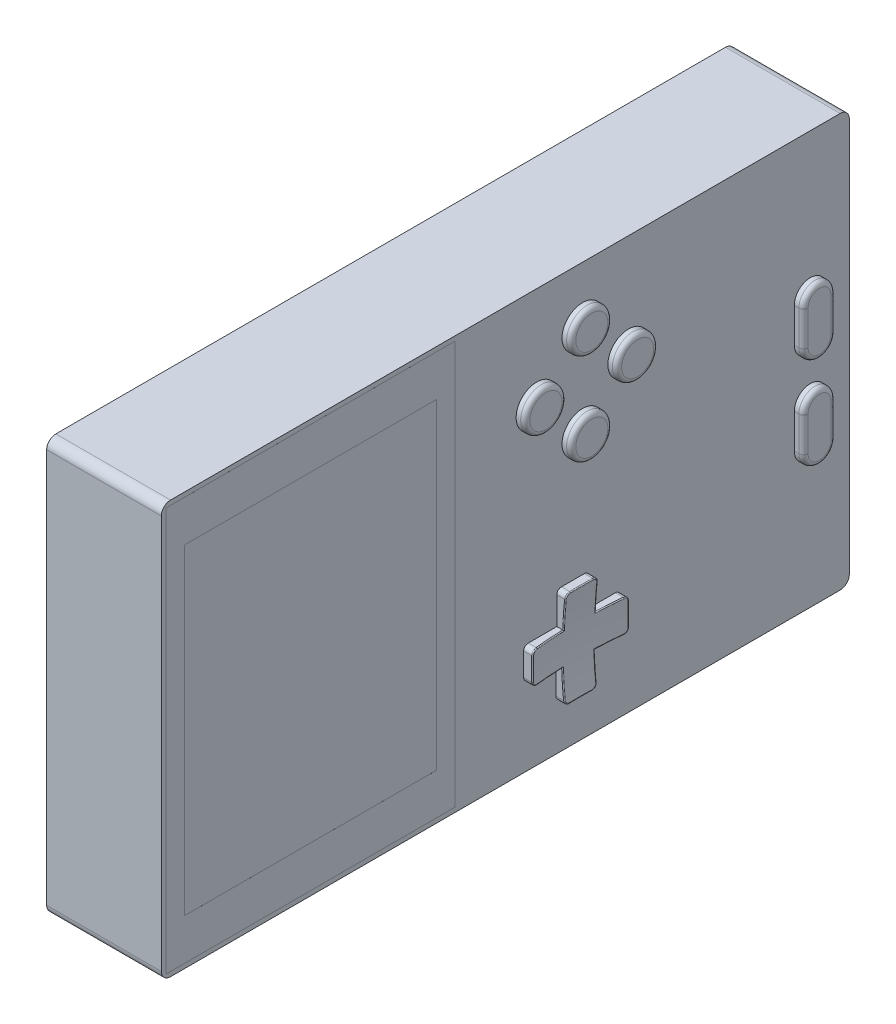
SolidWorks part; units mm, degrees
ref_plane "Front Plane" through (0, 0, 0) normal (1, 0, 0) x (0, 1, 0)
ref_plane "Top Plane" through (0, 0, 0) normal (0, 0, 1) x (0, 1, 0)
ref_plane "Right Plane" through (0, 0, 0) normal (0, 1, 0) x (-1, 0, 0)
sketch "Sketch1" plane through (0, 0, 0) normal (1, 0, 0) x (0, 1, 0)
  line L0 (0, -14.85) -> (0, 14.85) construction
  line L1 (-45, 75) -> (45, 75)
  line L2 (-45, 75) -> (-45, -75)
  line L3 (-45, -75) -> (45, -75)
  line L4 (45, 75) -> (45, -75)
  line L5 (-45, 75) -> (45, -75) construction
  line L6 (-45, -75) -> (45, 75) construction
  line L7 (-35, 70) -> (35, 70)
  line L8 (-35, 70) -> (-35, 15)
  line L9 (-35, 15) -> (35, 15)
  line L10 (35, 70) -> (35, 15)
  line L11 (-35, 70) -> (35, 15) construction
  line L12 (-35, 15) -> (35, 70) construction
  line L13 (-28, -11) -> (-28, -4)
  line L14 (-28, -4) -> (-21, -4)
  line L15 (-21, -4) -> (-21, -11.2367)
  line L16 (-21, -11.2367) -> (-14, -11.2367)
  line L17 (-14, -11.2367) -> (-14, -18.2367)
  line L18 (-14, -18.2367) -> (-21, -18.2367)
  line L19 (-21, -18.2367) -> (-21, -25)
  line L20 (-21, -25) -> (-28, -25)
  line L21 (-28, -25) -> (-28, -18)
  line L22 (-28, -18) -> (-35, -18)
  line L23 (-35, -18) -> (-35, -11)
  line L24 (-35, -11) -> (-28, -11)
  line L25 (13.75, -66.5) -> (6.25, -66.5) construction
  line L28 (-13.75, -66.5) -> (-6.25, -66.5) construction
  line L29 (-13.75, -63) -> (-6.25, -63)
  line L30 (-13.75, -70) -> (-6.25, -70)
  line L31 (0, 69.6676) -> (0, -69.6676)
  line L32 (13.75, -63) -> (6.25, -63)
  line L33 (13.75, -70) -> (6.25, -70)
  line L35 (44, 11) -> (-44, 11)
  line L36 (44, 11) -> (44, 74)
  line L37 (44, 74) -> (-44, 74)
  line L38 (-44, 11) -> (-44, 74)
  line L39 (44, 11) -> (-44, 74) construction
  line L40 (44, 74) -> (-44, 11) construction
  circle A0 centre (12.8731, -16.8512) radius 4.5
  circle A1 centre (22.8731, -6.8512) radius 4.5
  circle A2 centre (22.8731, -26.8512) radius 4.5
  circle A3 centre (32.8731, -16.8512) radius 4.5
  arc A6 (-13.75, -63) -> (-13.75, -70) centre (-13.75, -66.5) ccw
  arc A7 (-6.25, -70) -> (-6.25, -63) centre (-6.25, -66.5) ccw
  arc A8 (13.75, -63) -> (13.75, -70) centre (13.75, -66.5) cw
  arc A9 (6.25, -70) -> (6.25, -63) centre (6.25, -66.5) cw
  point P0 (0, 0)
  point P6 (0, 42.5)
  point P35 (10, -66.5)
  point P42 (-10, -66.5)
  point P48 (0, 42.5)
  point P52 (0, 42.5)
  dimension "D16" = 9
  dimension "D17" = 20
  dimension "D18" = 20
  dimension "D21" = 7
  dimension "D1" = 150
  dimension "D2" = 90
  dimension "D3" = 55
  dimension "D4" = 70
  dimension "D5" = 5
  dimension "D6" = 7
  dimension "D7" = 7
  dimension "D8" = 7
  dimension "D9" = 7
  dimension "D10" = 7
  dimension "D11" = 7
  dimension "D12" = 7
  dimension "D13" = 7
  dimension "D14" = 10
  dimension "D15" = 50
  dimension "D19" = 10
  dimension "D20" = 10
  dimension "D22" = 5
  dimension "D23" = 7.5
  dimension "D24" = 10
  dimension "D25" = 139.3353
  dimension "D26" = 1
  dimension "D27" = 1
extrude "Boss-Extrude1" add sketch "Sketch1" along normal blind 25 contours L4 L1 L2 L3 A7 L30 A6 L29 A3 A2 A1 A0 L23 L24 L13 L14 L15 L16 L17 L18 L19 L20 L21 L22 L35 L38 L37 L36 L33 A9 L32 A8 | A1 | A0 region at (0, 0.025, -29.6467)
extrude "Boss-Extrude2" add sketch "Sketch1<4>" along normal blind 25.001 contours L38 L35 L9 L8 L7 L10 L36 L37 region at (0, -22, 12.0823)
sketch "Sketch1<4>" plane through (0, 0, 0) normal (1, 0, 0) x (0, 1, 0) same geometry as "Sketch1"
extrude "Boss-Extrude3" add sketch "Sketch1<5>" along normal blind 25 separate body contours L8 L9 L10 L7
sketch "Sketch1<5>" plane through (0, 0, 0) normal (1, 0, 0) x (0, 1, 0) same geometry as "Sketch1"
extrude "Boss-Extrude4" add sketch "Sketch1<6>" along normal blind 27 contours A2 | A3 | L13 L14 L15 L16 L17 L18 L19 L20 L21 L22 L23 L24 | A1 | A0 region at (0, 22.8731, -26.8512) region at (0, 32.8731, -16.8512)
sketch "Sketch1<6>" plane through (0, 0, 0) normal (1, 0, 0) x (0, 1, 0) same geometry as "Sketch1"
extrude "Boss-Extrude5" add sketch "Sketch1<7>" along normal blind 27 contours L30 A7 L29 A6 | A9 L32 A8 L33 region at (0, -10, -66.5)
sketch "Sketch1<7>" plane through (0, 0, 0) normal (1, 0, 0) x (0, 1, 0) same geometry as "Sketch1"
fillet "Fillet1" radius 1 12 edges at (27, 22.8731, -31.3512) (26, -28, -4) (26, -35, -11) (26, -35, -18) (26, -28, -25) (26, -21, -25) (26, -21, -4) (26, -14, -11.2367) (26, -14, -18.2367) (27, 32.8731, -21.3512) (27, 12.8731, -21.3512) (27, 22.8731, -11.3512)
fillet "Fillet2" radius 1 8 edges at (27, 17.25, -66.5) (27, 10, -63) (27, 2.75, -66.5) (27, -17.25, -66.5) (27, -10, -63) (27, -2.75, -66.5) (27, 10, -70) (27, -10, -70)
sketch "Sketch3" plane through (0, 0, 0) normal (1, 0, 0) x (0, 1, 0)
  line L16 (45, 12.0067) -> (45, 8.0067)
  line L17 (45, 7.0067) -> (45, 3.0067)
  line L18 (45, 2.0067) -> (45, -1.9933)
  line L19 (45, -2.9933) -> (45, -6.9933)
  line L20 (45, -7.9933) -> (45, -11.9933)
  line L21 (45, -12.9933) -> (45, -16.9933)
  line L22 (45, -17.9933) -> (45, -21.9933)
  line L23 (45, -22.9933) -> (45, -26.9933)
  line L24 (45, -27.9933) -> (45, -31.9933)
  line L25 (45, -32.9933) -> (45, -36.9933)
  line L26 (45, -37.9933) -> (45, -41.9933)
  line L27 (45, -42.9933) -> (45, -46.9933)
  line L28 (45, -47.9933) -> (45, -51.9933)
  line L29 (45, -52.9933) -> (45, -56.9933)
  line L30 (45, -57.9933) -> (45, -61.9933)
  line L31 (45, -62.9933) -> (45, -66.9933)
  line L32 (45, -67.9933) -> (45, -71.9933)
  line L33 (45, -72.9933) -> (45, -76.9933)
  line L34 (45, -77.9933) -> (45, -81.9933)
  line L35 (45, -82.9933) -> (45, -86.9933)
  line L36 (0, -14.85) -> (0, 14.85) construction
  line L37 (-45, -12.9933) -> (-45, -16.9933)
  line L38 (-45, -17.9933) -> (-45, -21.9933)
  line L39 (-45, -22.9933) -> (-45, -26.9933)
  line L40 (-45, -27.9933) -> (-45, -31.9933)
  line L41 (-45, -32.9933) -> (-45, -36.9933)
  line L42 (-45, -37.9933) -> (-45, -41.9933)
  line L43 (-45, -42.9933) -> (-45, -46.9933)
  line L44 (-45, -47.9933) -> (-45, -51.9933)
  line L45 (-45, -52.9933) -> (-45, -56.9933)
  line L46 (-45, -57.9933) -> (-45, -61.9933)
  line L47 (-45, -62.9933) -> (-45, -66.9933)
  line L48 (-45, -67.9933) -> (-45, -71.9933)
  line L49 (-45, -72.9933) -> (-45, -76.9933)
  line L50 (-45, -77.9933) -> (-45, -81.9933)
  line L51 (-45, -82.9933) -> (-45, -86.9933)
  line L52 (-45, 12.0067) -> (-45, 8.0067)
  line L53 (-45, 7.0067) -> (-45, 3.0067)
  line L54 (-45, 2.0067) -> (-45, -1.9933)
  line L55 (-45, -2.9933) -> (-45, -6.9933)
  line L56 (-45, -7.9933) -> (-45, -11.9933)
  arc A0 (45, 12.0067) -> (45, 8.0067) centre (45, 10.0067) cw
  arc A1 (45, 7.0067) -> (45, 3.0067) centre (45, 5.0067) cw
  arc A2 (45, 2.0067) -> (45, -1.9933) centre (45, 0.0067) cw
  arc A3 (45, -2.9933) -> (45, -6.9933) centre (45, -4.9933) cw
  arc A4 (45, -7.9933) -> (45, -11.9933) centre (45, -9.9933) cw
  arc A5 (45, -12.9933) -> (45, -16.9933) centre (45, -14.9933) cw
  arc A6 (45, -17.9933) -> (45, -21.9933) centre (45, -19.9933) cw
  arc A7 (45, -22.9933) -> (45, -26.9933) centre (45, -24.9933) cw
  arc A8 (45, -27.9933) -> (45, -31.9933) centre (45, -29.9933) cw
  arc A9 (45, -32.9933) -> (45, -36.9933) centre (45, -34.9933) cw
  arc A10 (45, -37.9933) -> (45, -41.9933) centre (45, -39.9933) cw
  arc A11 (45, -42.9933) -> (45, -46.9933) centre (45, -44.9933) cw
  arc A12 (45, -47.9933) -> (45, -51.9933) centre (45, -49.9933) cw
  arc A13 (45, -52.9933) -> (45, -56.9933) centre (45, -54.9933) cw
  arc A14 (45, -57.9933) -> (45, -61.9933) centre (45, -59.9933) cw
  arc A15 (45, -62.9933) -> (45, -66.9933) centre (45, -64.9933) cw
  arc A16 (45, -67.9933) -> (45, -71.9933) centre (45, -69.9933) cw
  arc A17 (45, -72.9933) -> (45, -76.9933) centre (45, -74.9933) cw
  arc A18 (45, -77.9933) -> (45, -81.9933) centre (45, -79.9933) cw
  arc A19 (45, -82.9933) -> (45, -86.9933) centre (45, -84.9933) cw
  arc A20 (-45, -12.9933) -> (-45, -16.9933) centre (-45, -14.9933) ccw
  arc A21 (-45, -17.9933) -> (-45, -21.9933) centre (-45, -19.9933) ccw
  arc A22 (-45, -22.9933) -> (-45, -26.9933) centre (-45, -24.9933) ccw
  arc A23 (-45, -27.9933) -> (-45, -31.9933) centre (-45, -29.9933) ccw
  arc A24 (-45, -32.9933) -> (-45, -36.9933) centre (-45, -34.9933) ccw
  arc A25 (-45, -37.9933) -> (-45, -41.9933) centre (-45, -39.9933) ccw
  arc A26 (-45, -42.9933) -> (-45, -46.9933) centre (-45, -44.9933) ccw
  arc A27 (-45, -47.9933) -> (-45, -51.9933) centre (-45, -49.9933) ccw
  arc A28 (-45, -52.9933) -> (-45, -56.9933) centre (-45, -54.9933) ccw
  arc A29 (-45, -57.9933) -> (-45, -61.9933) centre (-45, -59.9933) ccw
  arc A30 (-45, -62.9933) -> (-45, -66.9933) centre (-45, -64.9933) ccw
  arc A31 (-45, -67.9933) -> (-45, -71.9933) centre (-45, -69.9933) ccw
  arc A32 (-45, -72.9933) -> (-45, -76.9933) centre (-45, -74.9933) ccw
  arc A33 (-45, -77.9933) -> (-45, -81.9933) centre (-45, -79.9933) ccw
  arc A34 (-45, -82.9933) -> (-45, -86.9933) centre (-45, -84.9933) ccw
  arc A35 (-45, -2.9933) -> (-45, -6.9933) centre (-45, -4.9933) ccw
  arc A36 (-45, -7.9933) -> (-45, -11.9933) centre (-45, -9.9933) ccw
  arc A37 (-45, 2.0067) -> (-45, -1.9933) centre (-45, 0.0067) ccw
  arc A38 (-45, 7.0067) -> (-45, 3.0067) centre (-45, 5.0067) ccw
  arc A39 (-45, 12.0067) -> (-45, 8.0067) centre (-45, 10.0067) ccw
  dimension "D1" = 2
  dimension "D3" = 5
  dimension "D2" = 20
extrude "Boss-Extrude6" [suppressed] add sketch "Sketch3" along normal up to surface (25 mm away) contours L44 A27 | L45 A28 | L46 A29 | A30 L47 | A31 L48 | A12 L28 | A13 L29 | A14 L30 | A15 L31 | A16 L32 | A11 L27 | A10 L26 | A25 L42 | A26 L43
fillet "Fillet3" [suppressed] radius 2
fillet "Fillet4" radius 2 4 edges at (12.5, 45, 75) (12.5, -45, 75) (12.5, -45, -75) (12.5, 45, -75)
ref_plane "Plane1" through (0, -24.5, 0) normal (0, 1, 0) x (-1, 0, 0)
sketch "Sketch4" plane through (0, -24.5, 0) normal (0, 1, 0) x (-1, 0, 0)
  line L0 (-27, -25.5) -> (-27, -3.5)
  line L1 (-26.511, -14.5) -> (-26.35, -14.5)
  line L2 (-26.511, -14.5) -> (-27, -14.5)
  arc A1 (-27, -25.5) -> (-27, -3.5) centre (-119.7519, -14.5) ccw
  point P0 (-26.2274, -14.5)
  point P3 (-26.35, -14.5)
  dimension "D1" = 0.65
  dimension "D2" = 22
ref_axis "Axis1" [suppressed] through (26.25, -24.5, -14.5) along (1, 0, 0)
revolve "Cut-Revolve5" cut sketch "Sketch4" angle 360 about axis through (26.25, -24.5, -14.5) along (1, 0, 0) region at (26.7399, -24.5, -10.3731)
fillet "Fillet7" radius 0.2 20 edges at (26.6338, -17.9966, -11.2367) (26.9626, -14.2167, -11.615) (26.9424, -14, -14.7368) (26.9671, -14.3738, -18.0164) (26.6508, -21, -21.1215) (26.9703, -21.3783, -24.7833) (26.9421, -24.5, -25) (26.9585, -27.7796, -24.6262) (26.6424, -31.0034, -18) (26.9703, -34.7833, -17.6217) (26.9421, -35, -14.5) (26.9585, -34.6262, -11.2204) (26.6343, -21, -8.1148) (26.9585, -21.2204, -4.3738) (26.9421, -24.5, -4) (26.9703, -27.6217, -4.2167) (26.6516, -17.9966, -18.2367) (26.6424, -28, -21.0034) (26.6424, -31.0034, -11) (26.6424, -28, -7.9966)
